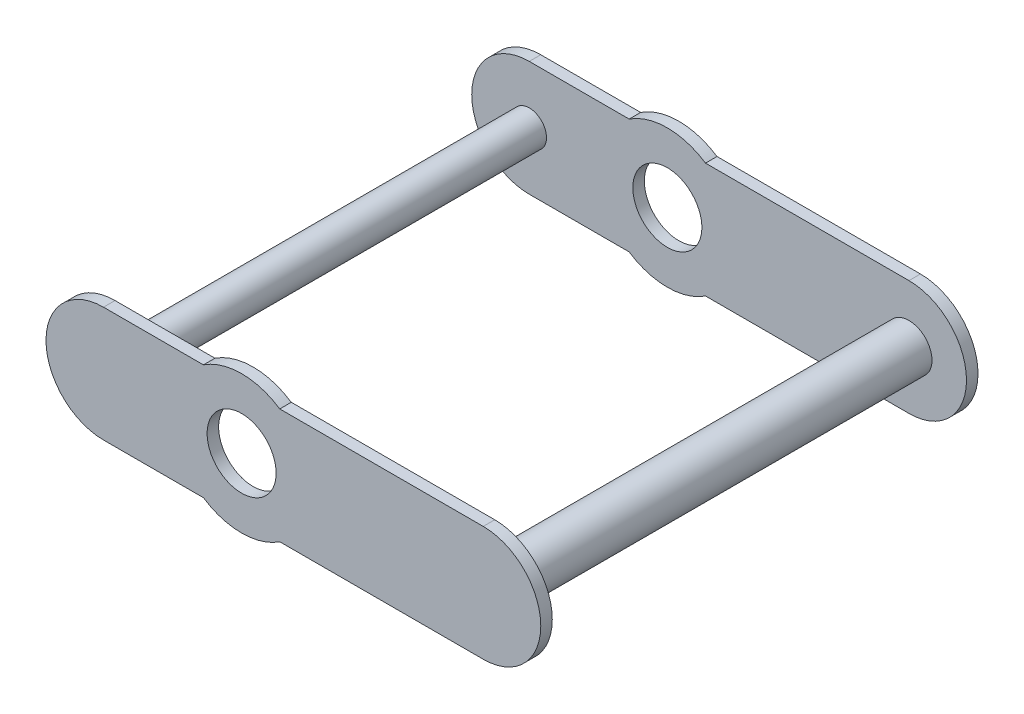
SolidWorks part; units mm, degrees
material "Plain Carbon Steel"
ref_plane "Front Plane" through (0, 0, 0) normal (0, 0, 1) x (1, 0, 0)
ref_plane "Top Plane" through (0, 0, 0) normal (0, 1, 0) x (1, 0, 0)
ref_plane "Right Plane" through (0, 0, 0) normal (1, 0, 0) x (0, 0, -1)
other "Center of Mass"
ref_axis "X" through (-88.99, 0, 0) along (1, 0, 0)
ref_axis "Y" through (0, 55, 0) along (0, -1, 0)
ref_axis "Z" through (0, 0, -88.99) along (0, 0, 1)
sketch "Sketch1" plane through (0, 0, 0) normal (0, 0, 1) x (1, 0, 0)
  line L0 (-152.4, 63.5) -> (-42.1211, 63.5)
  line L3 (42.1211, 63.5) -> (266.7, 63.5)
  line L4 (266.7, -63.5) -> (42.1211, -63.5)
  line L5 (-152.4, -63.5) -> (-42.1211, -63.5)
  line L6 (0, -76.2) -> (-152.4, -76.2) construction
  line L7 (-152.4, 0) -> (266.7, 0) construction
  arc A2 (42.1211, 63.5) -> (-42.1211, 63.5) centre (0, 0) ccw
  arc A3 (-152.4, 63.5) -> (-152.4, -63.5) centre (-152.4, 0) ccw
  arc A4 (266.7, 63.5) -> (266.7, -63.5) centre (266.7, 0) cw
  arc A5 (-42.1211, -63.5) -> (42.1211, -63.5) centre (0, 0) ccw
  circle A6 centre (0, 0) radius 38.1
  dimension "D3" = 76.2
  dimension "D5" = 76.2
  dimension "D1" = 152.4
  dimension "D2" = 266.7
  dimension "D4" = 12.7
extrude "Boss-Extrude1" add sketch "Sketch1" along normal mid plane 482.6
sketch "Sketch3" plane through (0, 0, 0) normal (0, 0, 1) x (1, 0, 0)
  circle A0 centre (0, 0) radius 330.2
  circle A1 centre (266.7, 0) radius 25.4
  circle A2 centre (-152.4, 0) radius 19.05
  arc A3 (266.7, -63.5) -> (266.7, 63.5) centre (266.7, 0) ccw construction
  circle A4 centre (-152.4, 0) radius 15.875
  dimension "D1" = 38.1
  dimension "D2" = 3.175
  dimension "D3" = 50.8
extrude "Cut-Extrude1" cut sketch "Sketch3" against normal mid plane 457.2 contours A0 A2 A1 | A4 region at (-1.0809, 0, 0) region at (-152.4, 0, 0)
